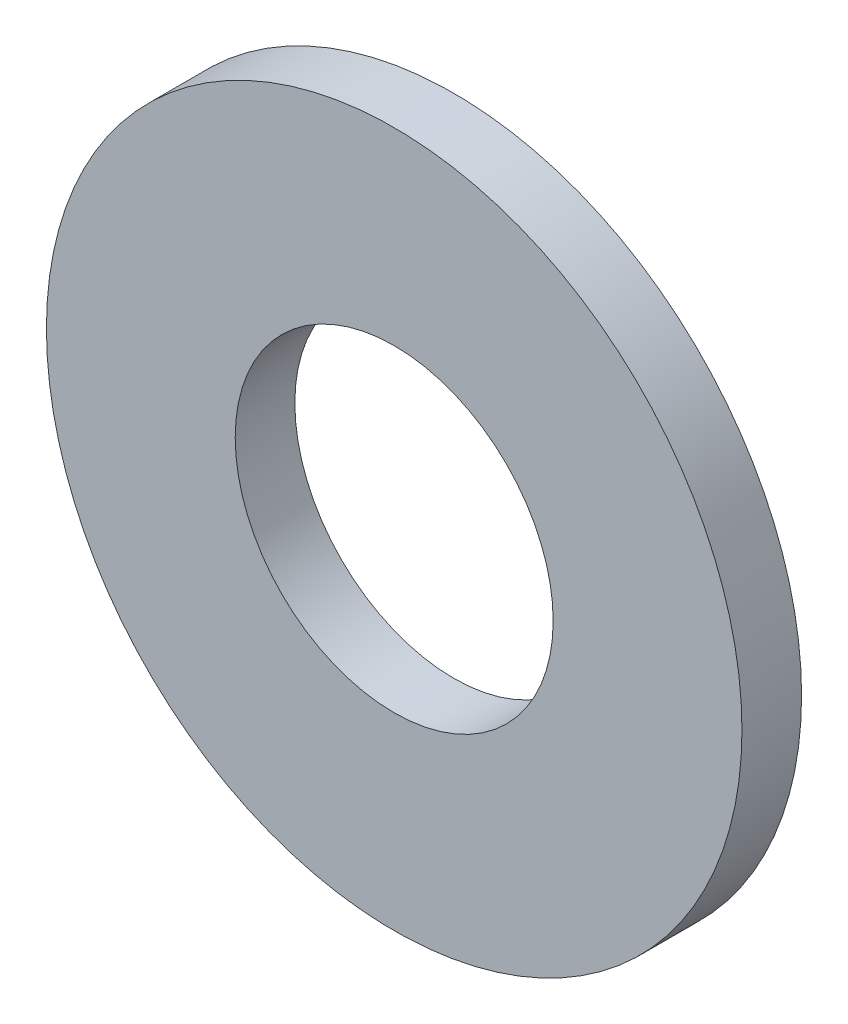
SolidWorks part; units mm, degrees
ref_plane "Front Plane" through (0, 0, 0) normal (0, 0, 1) x (1, 0, 0)
ref_plane "Top Plane" through (0, 0, 0) normal (0, 1, 0) x (1, 0, 0)
ref_plane "Right Plane" through (0, 0, 0) normal (1, 0, 0) x (0, 0, -1)
sketch "Sketch1" plane through (0, 0, 0) normal (0, 0, 1) x (1, 0, 0)
  circle A0 centre (0, 0) radius 3.5
  circle A1 centre (0, 0) radius 1.6
  dimension "OD" = 7
  dimension "ID1" = 3.2
extrude "Boss-Extrude1" add sketch "Sketch1" along normal blind 0.6
ref_axis "Axis1" through (0, 0, 0.63) along (0, 0, -1)
